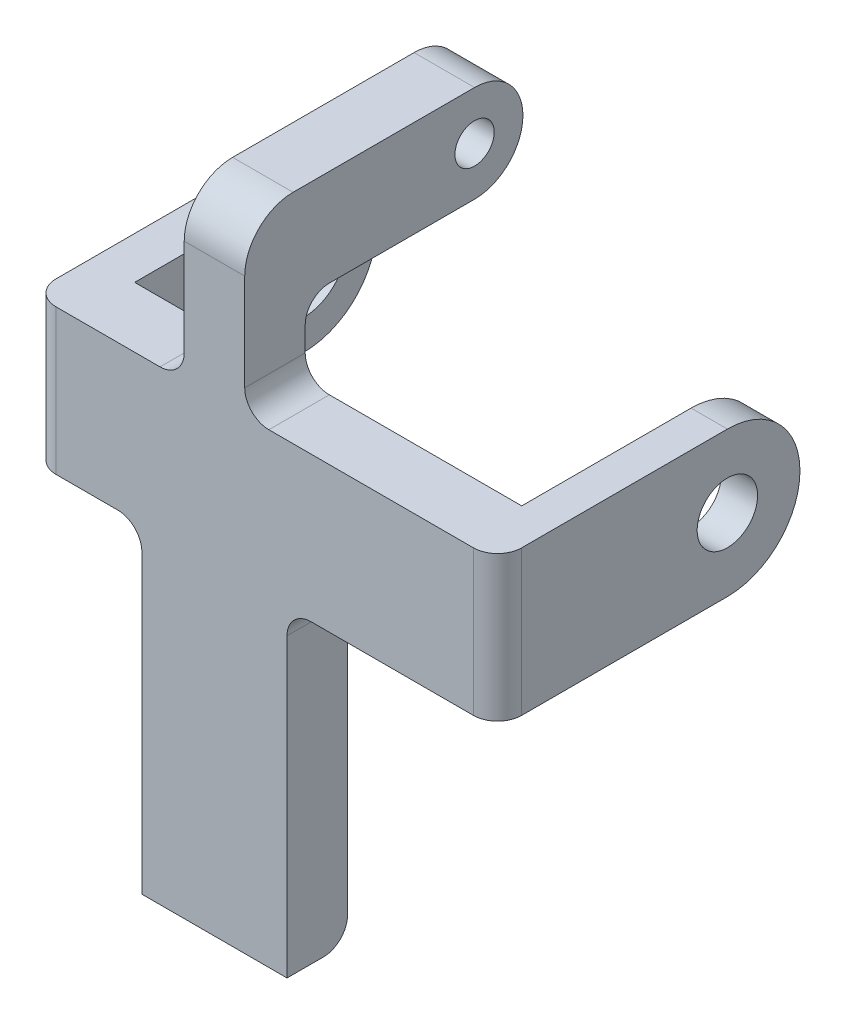
SolidWorks part; units mm, degrees
ref_plane "Front Plane" through (0, 0, 0) normal (0, 0, 1) x (1, 0, 0)
ref_plane "Top Plane" through (0, 0, 0) normal (0, 1, 0) x (1, 0, 0)
ref_plane "Right Plane" through (0, 0, 0) normal (1, 0, 0) x (0, 0, -1)
sketch "Sketch1" plane through (0, 0, 0) normal (0, 0, 1) x (1, 0, 0)
  line L0 (21.1, 0) -> (38.5, 0)
  line L1 (0, 0) -> (9.1, 0)
  line L2 (0, 0) -> (0, 12)
  line L3 (0, 12) -> (12.6, 12)
  line L4 (38.5, 0) -> (38.5, 12)
  line L5 (17.6, 12) -> (38.5, 12)
  line L6 (9.1, 0) -> (9.1, -26.5)
  line L7 (9.1, -26.5) -> (21.1, -26.5)
  line L8 (21.1, 0) -> (21.1, -26.5)
  line L10 (12.6, 12) -> (12.6, 26)
  line L11 (12.6, 26) -> (17.6, 26)
  line L12 (17.6, 12) -> (17.6, 26)
  dimension "D1" = 12
  dimension "D2" = 38.5
  dimension "D3" = 12
  dimension "D4" = 26.5
  dimension "D5" = 9.1
  dimension "D6" = 14
  dimension "D7" = 5
  dimension "D8" = 12.6
extrude "Boss-Extrude1" add sketch "Sketch1" along normal blind 5
sketch "Sketch2" plane through (0, 0, 0) normal (0, 0, -1) x (-1, 0, 0)
  line L0 (-12.6, 12) -> (0, 12) construction
  line L1 (0, 0) -> (-3.5, 0)
  line L2 (0, 0) -> (0, 12)
  line L3 (0, 12) -> (-3.5, 12)
  line L4 (-3.5, 0) -> (-3.5, 12)
  line L5 (-38.5, 12) -> (-17.6, 12) construction
  line L6 (-38.5, 0) -> (-35.5, 0)
  line L7 (-38.5, 0) -> (-38.5, 12)
  line L8 (-38.5, 12) -> (-35.5, 12)
  line L9 (-35.5, 0) -> (-35.5, 12)
  dimension "D1" = 3.5
  dimension "D2" = 3
extrude "Boss-Extrude2" add sketch "Sketch2" along normal blind 20
sketch "Sketch3" plane through (0, 0, 5) normal (0, 0, 1) x (1, 0, 0)
  line L0 (21.1, -26.5) -> (21.1, 0) construction
  line L1 (9.1, -26.5) -> (21.1, -26.5)
  line L2 (9.1, -26.5) -> (9.1, -23.5)
  line L3 (9.1, -23.5) -> (21.1, -23.5)
  line L4 (21.1, -26.5) -> (21.1, -23.5)
  line L5 (12.6, 12) -> (0, 12) construction
  line L6 (9.1, 12) -> (21.1, 12)
  line L7 (9.1, 12) -> (9.1, 8.5)
  line L8 (9.1, 8.5) -> (21.1, 8.5)
  line L9 (21.1, 12) -> (21.1, 8.5)
  line L10 (9.1, 0) -> (9.1, -26.5) construction
  dimension "D1" = 3
  dimension "D2" = 3.5
extrude "Boss-Extrude3" add sketch "Sketch3" along normal blind 20
sketch "Sketch4" plane through (0, 0, 0) normal (0, 0, -1) x (-1, 0, 0)
  line L0 (-12.6, 26) -> (-12.6, 12) construction
  line L1 (-17.6, 26) -> (-12.6, 26)
  line L2 (-17.6, 26) -> (-17.6, 18)
  line L3 (-17.6, 18) -> (-12.6, 18)
  line L4 (-12.6, 26) -> (-12.6, 18)
  dimension "D1" = 8
extrude "Boss-Extrude4" add sketch "Sketch4" along normal blind 18
sketch "Sketch5" plane through (0, 0, 0) normal (-1, 0, 0) x (0, 0, 1)
  line L0 (-20, 0) -> (-20, 12) construction
  line L1 (5, 12) -> (-20, 12) construction
  circle A0 centre (-14, 6) radius 3.5
  dimension "D3" = 7
  dimension "D1" = 6
  dimension "D2" = 6
extrude "Cut-Extrude1" cut sketch "Sketch5" against normal up to surface (3.5 mm away) up to face at (3.5, 7.5, -15)
sketch "Sketch6" plane through (0, 12, 0) normal (0, 1, 0) x (1, 0, 0)
  line L0 (21.1, -25) -> (21.1, -5) construction
  line L1 (21.1, -25) -> (9.1, -25) construction
  circle A0 centre (15.1, -19) radius 3.5
  dimension "D3" = 7
  dimension "D1" = 6
  dimension "D2" = 6
extrude "Cut-Extrude2" cut sketch "Sketch6" against normal up to surface (3.5 mm away) up to face at (15.1, 8.5, 15)
sketch "Sketch7" plane through (12.6, 0, 0) normal (-1, 0, 0) x (0, 0, 1)
  line L0 (-18, 18) -> (-18, 26) construction
  line L1 (5, 26) -> (-18, 26) construction
  circle A0 centre (-14, 22) radius 1.625
  dimension "D3" = 3.25
  dimension "D1" = 4
  dimension "D2" = 4
extrude "Cut-Extrude3" cut sketch "Sketch7" against normal up to surface (5 mm away) up to face at (17.6, 18.6667, -4.3333)
sketch "Sketch8" plane through (35.5, 0, 0) normal (-1, 0, 0) x (0, 0, 1)
  line L0 (-20, 0) -> (-20, 12) construction
  line L1 (-20, 12) -> (0, 12) construction
  circle A0 centre (-14, 6) radius 2.5
  dimension "D3" = 5
  dimension "D1" = 6
  dimension "D2" = 6
extrude "Cut-Extrude4" cut sketch "Sketch8" against normal up to surface (3 mm away) up to face at (38.5, 6, -7.5)
sketch "Sketch9" plane through (0, -23.5, 0) normal (0, 1, 0) x (1, 0, 0)
  line L0 (21.1, -25) -> (9.1, -25) construction
  line L1 (9.1, -25) -> (9.1, -5) construction
  circle A0 centre (15.1, -19) radius 2.5
  dimension "D3" = 5
  dimension "D1" = 6
  dimension "D2" = 6
extrude "Cut-Extrude5" cut sketch "Sketch9" against normal up to surface (3 mm away) up to face at (15.1, -26.5, 12.5)
fillet "Fillet1" radius 6 8 edges at (21.1, -25, 25) (9.1, -25, 25) (37, 0, -20) (37, 12, -20) (21.1, 10.25, 25) (9.1, 10.25, 25) (1.75, 0, -20) (1.75, 12, -20)
fillet "Fillet2" radius 2 4 edges at (15.1, 18, 0) (38.5, 6, 5) (0, 6, 5) (15.1, -26.5, 0)
fillet "Fillet3" radius 2 6 edges at (9.1, 0, 2.5) (21.1, 0, 2.5) (17.6, 12, 2.5) (12.6, 12, 2.5) (21.1, 10.25, 5) (9.1, 10.25, 5)
fillet "Fillet4" radius 4 3 edges at (15.1, 26, 5) (15.1, 26, -18) (15.1, 18, -18)
fillet "Fillet5" radius 8 1 edges at (15.1, 12, 5)
ref_plane "Plane1" through (0, 0, 5) normal (0, 0, 1) x (1, 0, 0)
other "SurfaceCut2"
